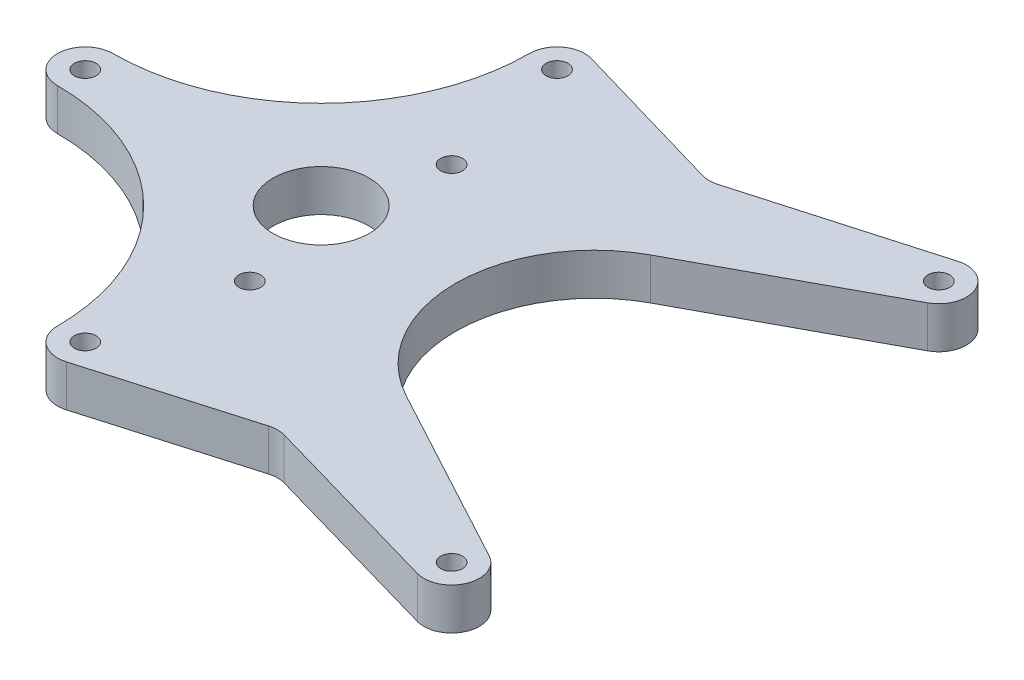
SolidWorks part; units mm, degrees
material "Alloy Steel"
ref_plane "Front Plane" through (0, 0, 0) normal (0, 0, 1) x (1, 0, 0)
ref_plane "Top Plane" through (0, 0, 0) normal (0, 1, 0) x (1, 0, 0)
ref_plane "Right Plane" through (0, 0, 0) normal (1, 0, 0) x (0, 0, -1)
sketch "Sketch2" plane through (0, 0, 0) normal (0, 1, 0) x (1, 0, 0)
  line L2 (62.5, 0) -> (12.5, 0) construction
  line L3 (12.5, 0) -> (0, 0) construction
  line L4 (62.5, 0) -> (179.6744, 0) construction
  line L5 (1.7741, 60.0721) -> (37.6405, 49.6359)
  line L6 (41.1613, -49.628) -> (83.8387, -61.8381)
  line L9 (62.5, 0) -> (85.5854, 55.733) construction
  line L10 (62.5, 0) -> (6.767, 23.0854) construction
  line L11 (0, 0) -> (-53.975, 0) construction
  line L12 (41.1613, 49.628) -> (83.8387, 61.8381)
  line L13 (0, 0) -> (0, 53.975) construction
  line L14 (1.7741, -60.0721) -> (37.6405, -49.6359)
  line L15 (62.5, 0) -> (39.4146, 55.733) construction
  line L21 (47.4315, 27.9464) -> (88.5991, 50.1438)
  line L22 (47.4315, -27.9464) -> (88.5991, -50.1438)
  arc A0 (47.4315, 27.9464) -> (47.4315, -27.9464) centre (62.5, 0) ccw
  circle A5 centre (0, 53.975) radius 2.4892
  circle A8 centre (6.767, 23.0854) radius 2.4892
  circle A9 centre (85.5854, 55.733) radius 2.4892
  circle A12 centre (85.5854, -55.733) radius 2.4892
  circle A13 centre (6.767, -23.0854) radius 2.4892
  circle A14 centre (0, -53.975) radius 2.4892
  circle A16 centre (0, 0) radius 11
  circle A19 centre (0, 53.975) radius 6.35
  circle A21 centre (85.5854, 55.733) radius 6.35
  circle A22 centre (85.5854, -55.733) radius 6.35
  circle A24 centre (0, -53.975) radius 6.35
  circle A26 centre (-53.975, 0) radius 2.4892
  circle A27 centre (-53.975, 0) radius 6.35
  arc A28 (-53.975, 6.35) -> (-6.35, 53.975) centre (-53.975, 53.975) ccw
  arc A29 (-53.975, -6.35) -> (-6.35, -53.975) centre (-53.975, -53.975) cw
  circle A31 centre (6.767, 23.0854) radius 6.35
  circle A32 centre (6.767, -23.0854) radius 6.35
  arc A34 (37.6405, 49.6359) -> (41.1613, 49.628) centre (39.4146, 55.733) ccw
  arc A35 (37.6405, -49.6359) -> (41.1613, -49.628) centre (39.4146, -55.733) cw
  dimension "D2" = 31.75
  dimension "D17" = 22
  dimension "D4" = 4.9784
  dimension "D3" = 12.7
  dimension "D10" = 6.35
  dimension "D5" = 50
  dimension "D6" = 12.5
  dimension "D7" = 67.5
  dimension "D8" = 22.5
  dimension "D9" = 45
  dimension "D12" = 60.325
  dimension "D14" = 53.975
extrude "Boss-Extrude1" add sketch "Sketch2" along normal mid plane 9.525 contours A24 A31 A22 L22 A0 L21 A21 A19 A16 | A19 A5 | A19 | A24 | A24 A14 | A31 A13 | A22 A12 | A21 A9 | A8 | A27 A26 region at (19.1403, 0, 0) region at (4.9351, 0, -57.6788) region at (-49.6119, 0, -4.3631) region at (89.3003, 0, -60.6598) region at (0, 0, 47.8046) region at (90.8837, 0, 52.5704) region at (0.5966, 0, -23.0854) region at (0.5966, 0, 23.0854)
ref_axis "Turbine Axis" through (0, 55, 0) along (0, -1, 0)
ref_axis "Pump Axis" through (62.5, 4.7625, 0) along (0, -1, 0)
